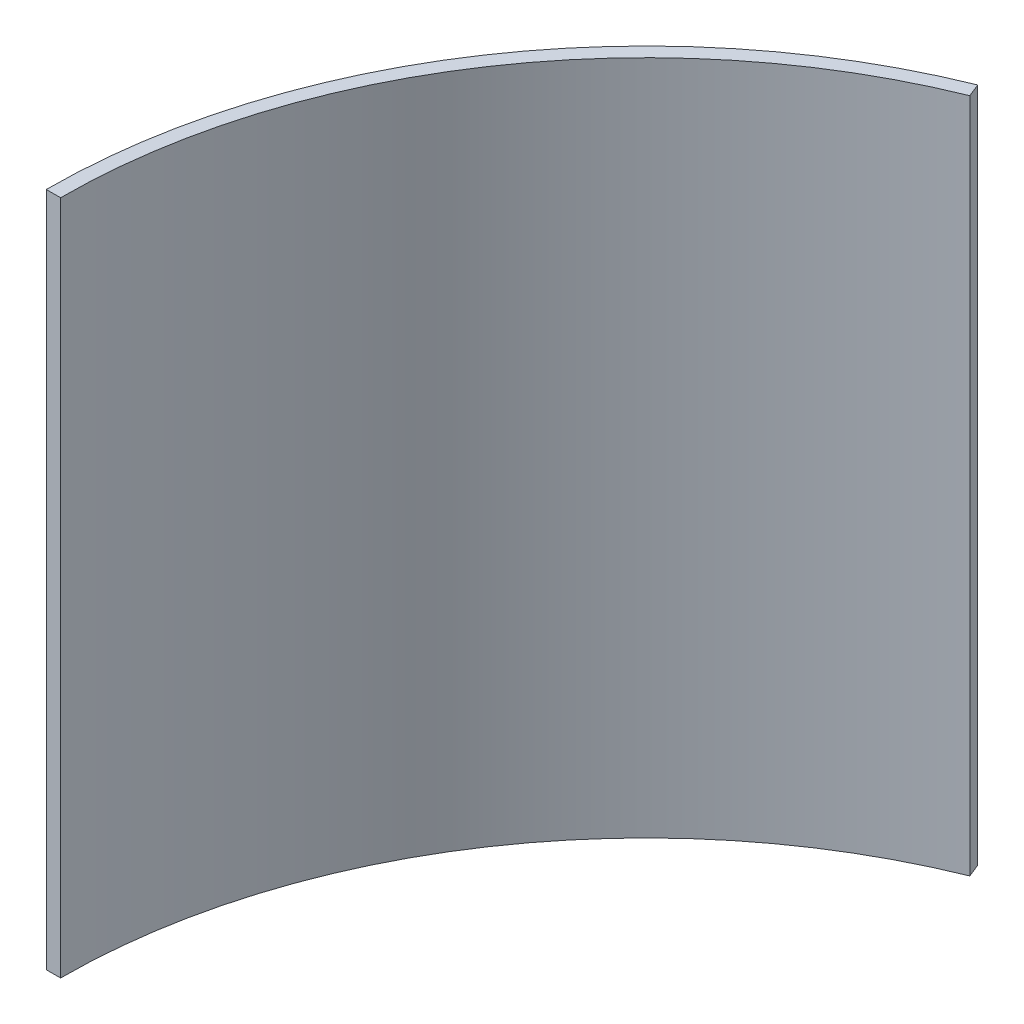
SolidWorks part; units mm, degrees
material "PC High Viscosity"
ref_plane "Front Plane" through (0, 0, 0) normal (0, 0, 1) x (1, 0, 0)
ref_plane "Top Plane" through (0, 0, 0) normal (0, 1, 0) x (1, 0, 0)
ref_plane "Right Plane" through (0, 0, 0) normal (1, 0, 0) x (0, 0, -1)
sketch "Sketch1" plane through (0, 0, 0) normal (0, 1, 0) x (1, 0, 0)
  line L0 (-130, 0) -> (-133.175, 0)
  line L1 (-48.6989, 120.5339) -> (-49.8882, 123.4777)
  arc A1 (-130, 0) -> (-48.6989, 120.5339) centre (0, 0) cw
  arc A2 (-133.175, 0) -> (-49.8882, 123.4777) centre (0, 0) cw
  point P1 (-42.0019, 123.0278)
  point P5 (0, 0)
  dimension "D1" = 130
  dimension "D2" = 68
  dimension "D3" = 3.175
extrude "Boss-Extrude1" add sketch "Sketch1" along normal blind 150
